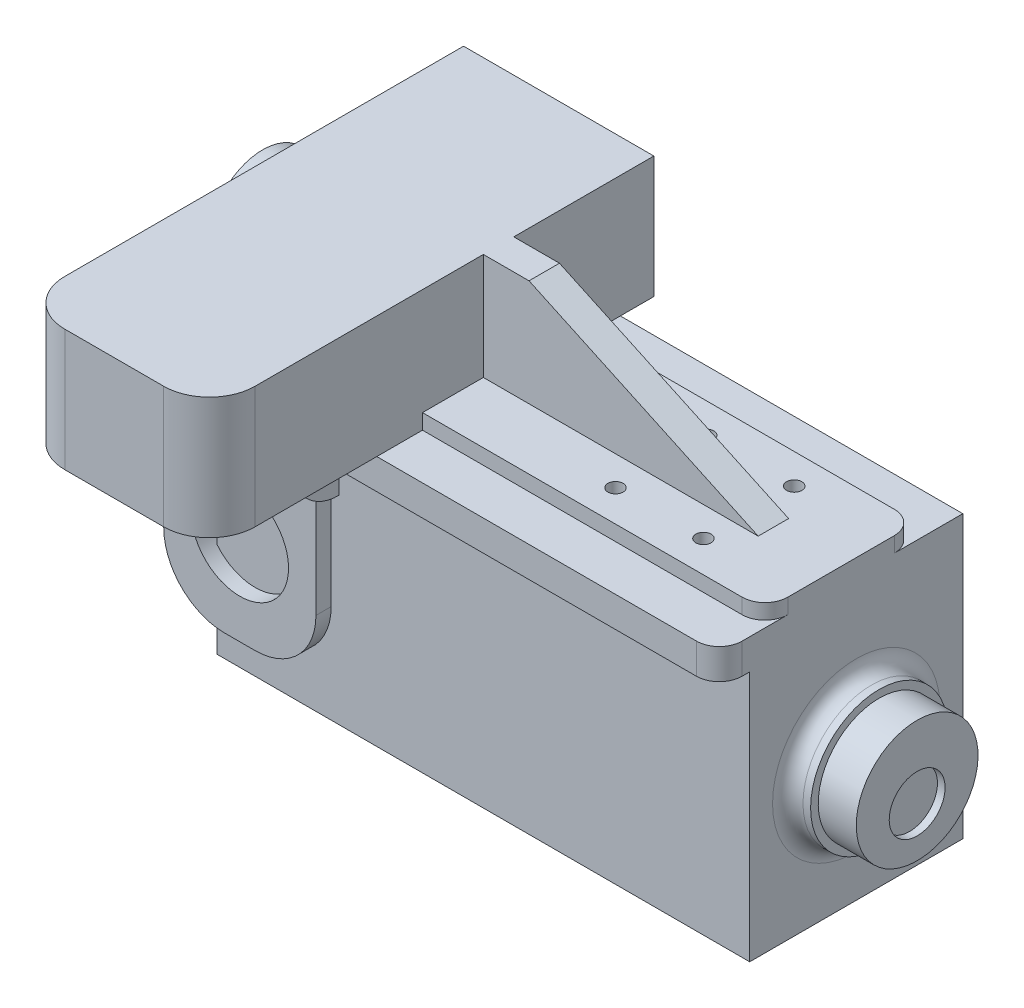
SolidWorks part; units mm, degrees
ref_plane "Front" through (0, 0, 0) normal (0, 0, 1) x (1, 0, 0)
ref_plane "Top" through (0, 0, 0) normal (0, 1, 0) x (1, 0, 0)
ref_plane "Right" through (0, 0, 0) normal (1, 0, 0) x (0, 0, -1)
sketch "Sketch1" plane through (0, 0, 0) normal (0, 1, 0) x (1, 0, 0)
  line L1 (-125, -115) -> (125, -115)
  line L2 (-125, -115) -> (-125, 115)
  line L3 (-125, 115) -> (125, 115)
  line L4 (125, -115) -> (125, 115)
  line L5 (-125, -115) -> (125, 115) construction
  line L6 (-125, 115) -> (125, -115) construction
  circle A0 centre (0, 0) radius 32
  circle A2 centre (0, 0) radius 45
  dimension "D1" = 64
  dimension "D2" = 250
  dimension "D4" = 90
  dimension "D3" = 230
extrude "Boss-Extrude1" add sketch "Sketch1" against normal blind 100 and the other way blind 150 contours L1 L4 L3 L2 A0 | A0 | A2 A0
sketch "Sketch2" plane through (125, 0, 0) normal (1, 0, 0) x (0, 0, -1)
  line L1 (-100, 0) -> (100, 0)
  line L2 (-100, 0) -> (-100, -30)
  line L3 (-100, -30) -> (100, -30)
  line L4 (100, 0) -> (100, -30)
  line L5 (115, -100) -> (115, 150) construction
  line L6 (-115, -100) -> (115, -100) construction
  dimension "D1" = 30
  dimension "D2" = 200
  dimension "D3" = 15
  dimension "D4" = 70
extrude "Boss-Extrude2" add sketch "Sketch2" along normal blind 150
sketch "Sketch4" plane through (0, 0, -115) normal (0, 0, -1) x (-1, 0, 0)
  line L0 (125, 95) -> (-225, 95)
  line L1 (125, 95) -> (125, 260)
  line L2 (-225, 95) -> (-225, 260)
  line L3 (125, 260) -> (-225, 260)
  line L4 (125, 150) -> (125, -100) construction
  line L5 (125, 150) -> (-125, 150) construction
  dimension "D1" = 0
  dimension "D2" = 55
  dimension "D3" = 350
  dimension "D4" = 165
extrude "Boss-Extrude3" add sketch "Sketch4" along normal blind 120 and the other way blind 20 contours L1 L3 L2 L0
sketch "Sketch5" plane through (0, 0, 0) normal (1, 0, 0) x (0, 0, -1)
  line L0 (-47.0359, 150) -> (95, 260)
  line L1 (-115, 150) -> (95, 150) construction
  line L2 (95, 95) -> (95, 260) construction
rib "Rib1" sketch "Sketch5" sketch "Sketch5" thickness 250 extrusion direction parallel to sketch draft on no parameters "D1"=250
sketch "Sketch6" plane through (225, 0, 0) normal (1, 0, 0) x (0, 0, -1)
  line L0 (235, 95) -> (235, 260) construction
  circle A0 centre (165, 177.5) radius 45
  point P4 (235, 177.5)
  dimension "D1" = 90
extrude "Boss-Extrude4" add sketch "Sketch6" along normal blind 15
sketch "Sketch7" plane through (240, 0, 0) normal (1, 0, 0) x (0, 0, -1)
  circle A0 centre (165, 177.5) radius 40
  circle A1 centre (165, 177.5) radius 45
  circle A2 centre (165, 177.5) radius 45 construction
  dimension "D2" = 80
  dimension "D1" = 0
extrude "Boss-Extrude5" add sketch "Sketch7" along normal blind 20
sketch "Sketch8" plane through (0, 116.5332, 90.2494) normal (0, 0.7906, 0.6123) x (1, 0, 0)
  line L0 (-125, 54.6574) -> (125, 234.3076) construction
  line L2 (-50, 94.4825) -> (50, 94.4825)
  line L3 (-50, 94.4825) -> (-50, 194.4825)
  line L4 (-125, 234.3076) -> (-125, 54.6574)
  line L5 (-125, 54.6574) -> (125, 54.6574)
  line L6 (125, 54.6574) -> (125, 234.3076)
  line L7 (125, 234.3076) -> (-125, 234.3076)
  line L8 (-125, 234.3076) -> (-125, 54.6574) construction
  line L9 (-125, 54.6574) -> (125, 54.6574) construction
  line L10 (125, 54.6574) -> (125, 234.3076) construction
  line L11 (125, 234.3076) -> (-125, 234.3076) construction
  line L12 (-50, 194.4825) -> (50, 194.4825)
  line L13 (50, 94.4825) -> (50, 194.4825)
  line L14 (-50, 94.4825) -> (50, 194.4825) construction
  line L15 (-50, 194.4825) -> (50, 94.4825) construction
  point P2 (0, 144.4825)
  dimension "D2" = 100
  dimension "D3" = 100
  dimension "D1" = 0
sketch "Sketch9" plane through (0, 0, 0) normal (1, 0, 0) x (0, 0, -1)
  line L0 (95, 260) -> (-47.0359, 150) construction
  arc A0 (23.982, 205) -> (-5.2889, 293.9833) centre (173.6256, 303.531) cw
sweep "Sweep1" add profiles "Sketch8" path "Sketch9"
sketch "Sketch10" plane through (125, 0, 0) normal (1, 0, 0) x (0, 0, -1)
  line L0 (95, 214.2731) -> (75, 214.2731)
  line L2 (95, 95) -> (95, 260) construction
  line L3 (75, 214.2731) -> (75, 114.2731)
  line L4 (75, 114.2731) -> (95, 114.2731)
  line L5 (95, 214.2731) -> (95, 114.2731)
  dimension "D1" = 20
  dimension "D2" = 100
extrude "Boss-Extrude6" add sketch "Sketch10" along normal blind 150 contours L3 L4 L5 L0
ref_plane "Plane1" through (0, 164.2731, 0) normal (0, -1, 0) x (-1, 0, 0)
sketch "Sketch12" plane through (0, 164.2731, 0) normal (0, -1, 0) x (-1, 0, 0)
  line L0 (-125, 0) -> (-196.5844, 71.5844)
  line L1 (-125, 100) -> (-125, -100) construction
rib "Rib2" sketch "Sketch12" sketch "Sketch12" thickness 20 extrusion direction parallel to sketch draft on no parameters "D1"=20
sketch "Sketch13" plane through (0, -30, 0) normal (0, -1, 0) x (1, 0, 0)
  line L0 (275, 100) -> (275, -100) construction
  circle A0 centre (218.8697, 0) radius 32
  point P5 (275, 0)
  dimension "D1" = 64
extrude "Cut-Extrude1" cut sketch "Sketch13" against normal blind 10
fillet "Fillet1" radius 50 2 edges at (275, -15, -100) (275, -15, 100)
fillet "Fillet2" radius 30 1 edges at (125, 95, -105)
fillet "Fillet3" radius 15 2 edges at (125, 214.2731, -85) (125, 114.2731, -85)
fillet "Fillet4" radius 15 4 edges at (-50, 205, -23.982) (0, 235.615, -63.5133) (50, 205, -23.982) (0, 174.385, 15.5492)
fillet "Fillet5" [suppressed] radius 15
sketch "Sketch14" plane through (260, 0, 0) normal (1, 0, 0) x (0, 0, -1)
  circle A0 centre (165, 170) radius 18.3604
  circle A1 centre (165, 177.5) radius 40
  circle A4 centre (165, 177.5) radius 40
  dimension "D1" = 0
extrude "Boss-Extrude7" add sketch "Sketch14" along normal blind 5
fillet "Fillet6" radius 10 1 edges at (225, 222.5, -165)
sketch "Sketch15" plane through (0, -100, 0) normal (0, -1, 0) x (1, 0, 0)
  line L1 (-85, -82.836) -> (85, -82.836)
  line L2 (-85, -82.836) -> (-85, 82.836)
  line L3 (-85, 82.836) -> (85, 82.836)
  line L4 (125, 115) -> (-125, 115)
  line L5 (-125, 115) -> (-125, -115)
  line L6 (-125, -115) -> (125, -115)
  line L7 (125, -115) -> (125, 115)
  line L8 (125, 115) -> (-125, 115)
  line L9 (-125, 115) -> (-125, -115)
  line L10 (-125, -115) -> (125, -115)
  line L11 (125, -115) -> (125, 115)
  line L12 (85, -82.836) -> (85, 82.836)
  line L13 (-85, -82.836) -> (85, 82.836) construction
  line L14 (-85, 82.836) -> (85, -82.836) construction
  point P2 (0, 0)
  dimension "D2" = 40
  dimension "D1" = 0
extrude "Cut-Extrude2" cut sketch "Sketch15" against normal blind 40
sketch "Sketch16" plane through (-125, 0, 0) normal (-1, 0, 0) x (0, 0, 1)
  line L0 (82.836, -60) -> (-82.836, -60) construction
  circle A0 centre (0, 30) radius 50
  circle A1 centre (0, 30) radius 30
  point P4 (0, -60)
  dimension "D1" = 90
  dimension "D2" = 100
  dimension "D3" = 60
extrude "Boss-Extrude8" add sketch "Sketch16" along normal blind 30
extrude "Boss-Extrude9" add sketch "Sketch16<2>" along normal blind 50 contours A1
sketch "Sketch16<2>" plane through (-125, 0, 0) normal (-1, 0, 0) x (0, 0, 1) same geometry as "Sketch16"
sketch "Sketch17" plane through (0, 0, -95) normal (0, 0, 1) x (1, 0, 0)
  line L2 (-349.8788, -134.3572) -> (437.5635, -134.3572)
  line L3 (-349.8788, -134.3572) -> (-349.8788, 334.2136)
  line L4 (-349.8788, 334.2136) -> (437.5635, 334.2136)
  line L5 (437.5635, -134.3572) -> (437.5635, 334.2136)
  line L6 (-349.8788, -134.3572) -> (437.5635, 334.2136) construction
  line L7 (-349.8788, 334.2136) -> (437.5635, -134.3572) construction
  point P1 (43.8424, 99.9282)
extrude "Cut-Extrude3" cut sketch "Sketch17" along normal through all
sketch "Sketch18" plane through (0, 95, 0) normal (0, -1, 0) x (1, 0, 0)
  line L1 (-274.289, -308.2607) -> (480.5316, -308.2607)
  line L2 (-274.289, -308.2607) -> (-274.289, -11.2095)
  line L3 (-274.289, -11.2095) -> (480.5316, -11.2095)
  line L4 (480.5316, -308.2607) -> (480.5316, -11.2095)
  line L5 (-274.289, -308.2607) -> (480.5316, -11.2095) construction
  line L6 (-274.289, -11.2095) -> (480.5316, -308.2607) construction
  point P0 (103.1213, -159.7351)
extrude "Cut-Extrude4" cut sketch "Sketch18" along normal through all
sketch "Sketch19" plane through (0, 0, -95) normal (0, 0, -1) x (-1, 0, 0)
  line L0 (-225, 260) -> (125, 95) construction
  line L1 (-50, 177.5) -> (100, 177.5) construction
  line L2 (125, 260) -> (125, 177.5)
  line L3 (125, 177.5) -> (100, 95)
  line L4 (125, 95) -> (125, 260)
  line L5 (125, 260) -> (-225, 260)
  line L6 (-225, 260) -> (-225, 95)
  line L7 (-225, 95) -> (125, 95)
  line L8 (125, 95) -> (125, 260) construction
  line L10 (-225, 260) -> (-225, 95) construction
  line L11 (-225, 95) -> (125, 95) construction
  line L12 (100, 95) -> (44.808, 161.22)
  line L15 (100, 177.5) -> (100, 95) construction
  line L16 (44.808, 161.22) -> (44.808, 260)
  line L17 (125, 260) -> (-225, 260) construction
  line L18 (44.808, 260) -> (125, 260)
  circle A0 centre (100, 177.5) radius 32
  line M33 (125, 260) -> (125, 95)
  line M36 (-225, 260) -> (125, 260)
  dimension "D2" = 64
  dimension "D3" = 150
  dimension "D4" = 39.81
  dimension "D1" = 0
extrude "Boss-Extrude10" add sketch "Sketch19" against normal blind 30 contours A0 | L12 L16 L3 A0 M36 M33 region at (-123.1654, 228.7375, -95) region at (-97.543, 177.9707, -95)
sketch "Sketch20" plane through (0, 0, -95) normal (0, 0, 1) x (1, 0, 0)
  line L0 (-50, 260) -> (-50, 159.6056)
  line L1 (-44.808, 260) -> (225, 260) construction
  line L2 (-90, 119.6056) -> (-110, 119.6056)
  line L3 (-150, 159.6056) -> (-150, 260)
  line L4 (-150, 260) -> (-50, 260)
  circle A0 centre (-100, 177.5) radius 32 construction
  circle A1 centre (-100, 177.5) radius 32
  arc A2 (-110, 119.6056) -> (-150, 159.6056) centre (-110, 159.6056) cw
  arc A3 (-50, 159.6056) -> (-90, 119.6056) centre (-90, 159.6056) cw
  dimension "D3" = 40
  dimension "D1" = 50
  dimension "D2" = 50
sketch "Sketch22" plane through (0, 260, 0) normal (0, 1, 0) x (1, 0, 0)
  line L0 (225, 95) -> (225, 75)
  line L1 (225, 75) -> (-44.808, 75)
  line L6 (225, 95) -> (225, 235)
  line L7 (225, 235) -> (-125, 235)
  line L8 (-125, 235) -> (-125, 65)
  line L9 (-125, 65) -> (-44.808, 65)
  line L10 (-44.808, 65) -> (-44.808, 95)
  line L11 (-44.808, 95) -> (225, 95)
  line L12 (225, 95) -> (225, 235)
  line L13 (225, 235) -> (-125, 235)
  line L14 (-125, 235) -> (-125, 65)
  line L15 (-125, 65) -> (-44.808, 65)
  line L16 (-44.808, 65) -> (-44.808, 75)
  dimension "D1" = 0
extrude "Boss-Extrude11" add sketch "Sketch22" along normal blind 20 contours L1 L16 L15 L14 L13 L12 L0
sketch "Sketch23" plane through (0, 0, -65) normal (0, 0, 1) x (1, 0, 0)
  line L0 (-125, 280) -> (-125, 360)
  line L1 (-125, 360) -> (0, 360)
  line L2 (0, 360) -> (0, 280)
  line L3 (225, 280) -> (-44.808, 280) construction
  line L4 (0, 280) -> (-125, 280)
  dimension "D1" = 80
  dimension "D2" = 125
extrude "Boss-Extrude12" add sketch "Sketch23" against normal blind 192 and the other way blind 100
sketch "Sketch24" plane through (0, 0, -65) normal (0, 0, 1) x (1, 0, 0)
  line L0 (-44.808, 260) -> (-125, 260)
  line L1 (-125, 280) -> (-125, 177.5) construction
  line L2 (-125, 260) -> (-125, 220.61)
  line L3 (-125, 220.61) -> (-44.808, 220.61)
  line L4 (-44.808, 161.22) -> (-44.808, 280) construction
  line L5 (-44.808, 220.61) -> (-44.808, 260)
extrude "Cut-Extrude7" [suppressed] cut sketch "Sketch24" against normal blind 50
sketch "Sketch26" plane through (-44.808, 0, 0) normal (1, 0, 0) x (0, 0, -1)
  line L1 (56.5644, 225.5366) -> (56.5644, 95)
  line L2 (65, 95) -> (95, 95) construction
  line L3 (56.5644, 95) -> (95, 95)
  line L4 (95, 95) -> (95, 225.5366)
  line L5 (56.5644, 225.5366) -> (95, 225.5366)
extrude "Cut-Extrude8" cut sketch "Sketch26" against normal blind 196
sketch "Sketch27" plane through (0, 280, 0) normal (0, 1, 0) x (1, 0, 0)
  line L0 (0, 205) -> (0, 105)
  line L1 (0, 205) -> (225, 205)
  line L2 (0, 105) -> (225, 105)
  line L3 (225, 205) -> (225, 105)
  line L4 (0, 235) -> (0, 75) construction
  line L5 (0, 257) -> (0, -35) construction
  line L6 (225, 235) -> (0, 235) construction
  line L7 (225, 75) -> (0, 75) construction
  line L8 (225, 235) -> (225, 75) construction
  dimension "D1" = 30
  dimension "D2" = 30
extrude "Boss-Extrude14" add sketch "Sketch27" along normal blind 10
ref_plane "Plane3" through (0, 0, -155) normal (0, 0, 1) x (1, 0, 0)
sketch "Sketch28" plane through (0, 0, -155) normal (0, 0, 1) x (1, 0, 0)
  line L0 (0, 360) -> (0, 290)
  line L1 (0, 290) -> (180.5561, 290)
  line L2 (0, 290) -> (225, 290) construction
  line L3 (180.5561, 290) -> (30, 360)
  line L4 (0, 360) -> (30, 360)
  dimension "D1" = 30
  dimension "D2" = 70
extrude "Boss-Extrude15" add sketch "Sketch28" along normal blind 10 and the other way blind 10
sketch "Sketch29" plane through (-125, 0, 0) normal (-1, 0, 0) x (0, 0, 1)
  line L0 (-65, 280) -> (-65, 225.5366) construction
  circle A0 centre (-145, 312.0561) radius 35
  dimension "D1" = 70
  dimension "D2" = 80
extrude "Boss-Extrude16" add sketch "Sketch29" along normal blind 20
fillet "Fillet7" radius 15 1 edges at (225, 270, -75)
fillet "Fillet9" radius 15 2 edges at (225, 285, -205) (225, 285, -105)
sketch "Sketch31" plane through (0, 290, 0) normal (0, 1, 0) x (1, 0, 0)
  circle A0 centre (106.1298, 125.6853) radius 5
  circle A1 centre (163.9122, 125.6853) radius 5
  circle A2 centre (230.1765, 125.6853) radius 5
  circle A3 centre (163.9122, 185.3231) radius 5
  circle A4 centre (106.1298, 185.3231) radius 5
  circle A5 centre (230.1765, 185.3231) radius 5
sketch "Sketch33" plane through (0, 0, -235) normal (0, 0, -1) x (-1, 0, 0)
  line L4 (-225, 95) -> (-225, 280) construction
  circle A0 centre (-145, 180) radius 40
  dimension "D1" = 80
extrude "Boss-Extrude17" add sketch "Sketch33" along normal blind 20
extrude "Cut-Extrude10" cut sketch "Sketch31" against normal blind 10
extrude "Boss-Extrude18" add sketch "Sketch20" along normal blind 10 and the other way blind 20
fillet "Fillet10" radius 30 3 edges at (-84.904, 225.5366, -65) (-125, 320, 35) (0, 320, 35)
scale "Scale1" scale about centroid uniform scaling yes scale factor 0.6
